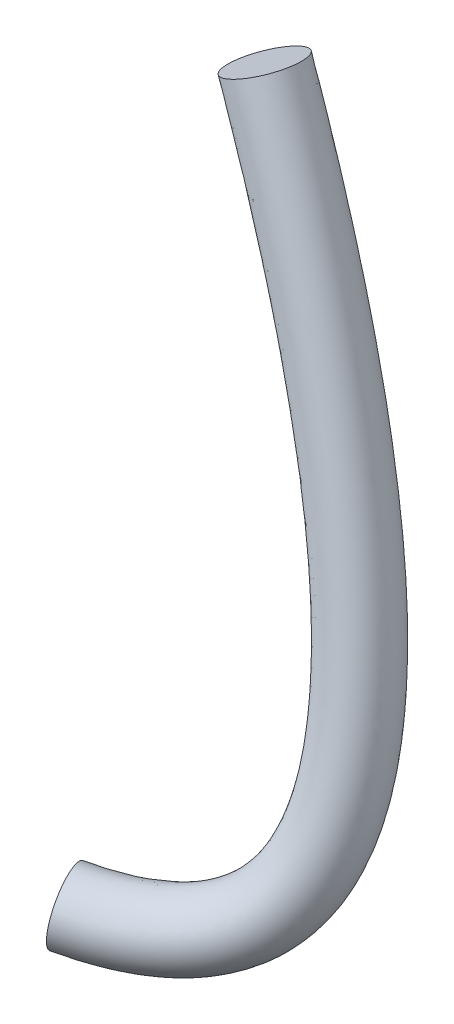
SolidWorks part; units mm, degrees
material "Custom Plastic"
ref_plane "X-Y Datum" through (0, 0, 0) normal (0, 0, 1) x (1, 0, 0)
ref_plane "X-Z Datum" through (0, 0, 0) normal (0, 1, 0) x (1, 0, 0)
ref_plane "Y-Z Datum" through (0, 0, 0) normal (1, 0, 0) x (0, 0, -1)
sketch3d "3DSketch1"
  circle A1 centre (183.4394, -113.2479, 219.825) radius 4.5 construction
  circle A2 centre (183.9425, -173.6243, 236.269) radius 2.8519 construction
  spline S0 degree 2 poles (183.4394, -113.2479, 219.825) (212.729, -177.9279, 224.7149) (182.1203, -173.4123, 237.0171) knots 0 0 0 1 1 1
  point P8 (185.3412, -117.3262, 219.825)
  point P11 (181.1878, -174.3624, 236.269)
sweep "Sweep1" add path "3DSketch1" circular profile diameter 6.35 parameters "D3"=6.35
